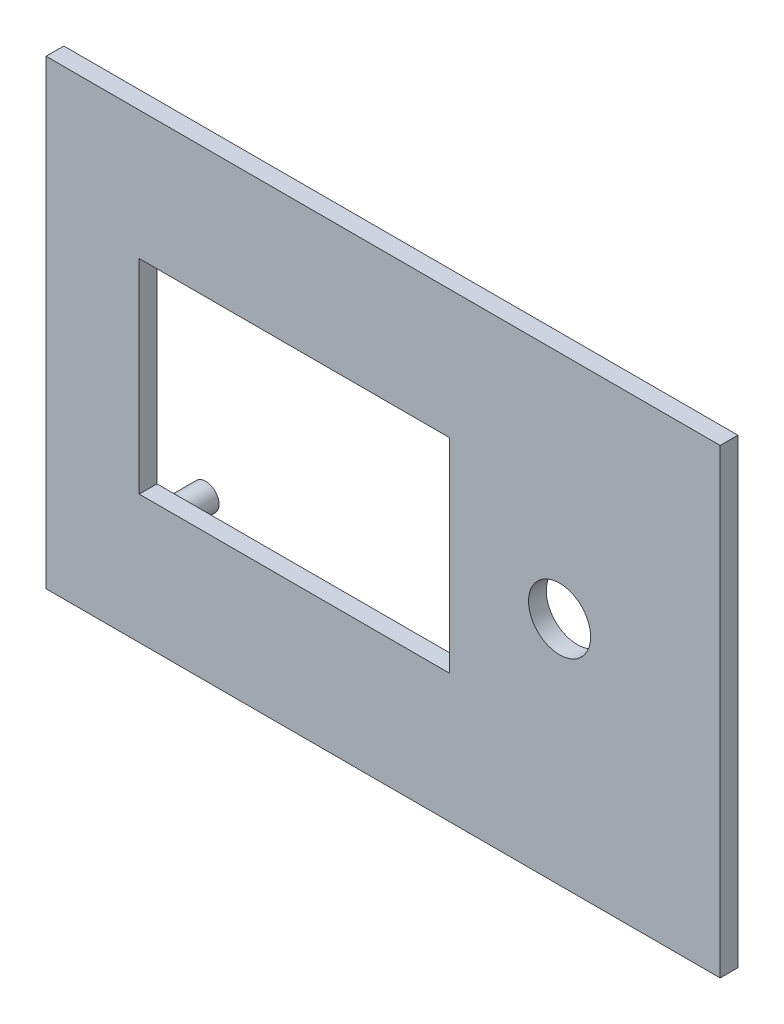
SolidWorks part; units mm, degrees
ref_plane "Ebene vorne" through (0, 0, 0) normal (0, 0, 1) x (1, 0, 0)
ref_plane "Ebene oben" through (0, 0, 0) normal (0, 1, 0) x (1, 0, 0)
ref_plane "Ebene rechts" through (0, 0, 0) normal (1, 0, 0) x (0, 0, -1)
sketch "Skizze10" plane through (0, 0, 0) normal (0, 0, 1) x (1, 0, 0)
  line L1 (-56.4904, -2.4023) -> (19.5096, -2.4023)
  line L2 (-56.4904, -2.4023) -> (-56.4904, -54.4023)
  line L3 (-56.4904, -54.4023) -> (19.5096, -54.4023)
  line L4 (19.5096, -2.4023) -> (19.5096, -54.4023)
  dimension "D1" = 76
  dimension "D2" = 52
extrude "Aufsatz-Linear austragen8" add sketch "Skizze10" along normal blind 2
sketch "Skizze11" plane through (0, 0, 2) normal (0, 0, 1) x (1, 0, 0)
  line L0 (-53.3332, -28.4023) -> (19.5096, -28.4023) construction
  line L1 (-45.987, -16.9023) -> (-10.987, -16.9023)
  line L2 (-45.987, -16.9023) -> (-45.987, -39.9023)
  line L3 (-45.987, -39.9023) -> (-10.987, -39.9023)
  line L4 (-10.987, -16.9023) -> (-10.987, -39.9023)
  line L5 (19.5096, -54.4023) -> (19.5096, -2.4023) construction
  point P6 (19.5096, -28.4023)
  dimension "D1" = 35
  dimension "D2" = 23
extrude "Schnitt-Linear austragen3" cut sketch "Skizze11" against normal blind 2
sketch "Skizze13" plane through (0, 0, 2) normal (0, 0, 1) x (1, 0, 0)
  line L1 (-53.9033, -28.4023) -> (16.6088, -28.4023) construction
  line L2 (-10.987, -16.9023) -> (-45.987, -16.9023) construction
  line L3 (-45.987, -39.9023) -> (-10.987, -39.9023) construction
  circle A0 centre (1.4022, -28.4023) radius 3.5
  point P2 (2.7784, -26.8523)
  point P3 (1.4022, -28.4023)
  point P5 (0, 0)
  point P8 (2.7784, 0.7098)
  point P9 (2.6375, 6.7112)
  point P10 (2.7784, -3.8165)
  point P15 (-53.9033, -28.4023)
  point P16 (16.6088, -28.4023)
  point P17 (1.9388, -28.4023)
  dimension "D1" = 7
extrude "Schnitt-Linear austragen4" cut sketch "Skizze13" against normal blind 2 contours A0
sketch "Skizze14" plane through (0, 0, 0) normal (0, 0, -1) x (-1, 0, 0)
  line L0 (10.987, -16.9023) -> (45.987, -16.9023) construction
  line L1 (45.987, -39.9023) -> (10.987, -39.9023) construction
  line L2 (45.987, -39.9023) -> (10.987, -39.9023) construction
  line L5 (45.987, -16.9023) -> (45.987, -39.9023) construction
  line L6 (10.987, -39.9023) -> (10.987, -16.9023) construction
  circle A0 centre (44.487, -14.4023) radius 1.5
  circle A1 centre (44.487, -42.4023) radius 1.5
  circle A2 centre (12.487, -14.4023) radius 1.5
  circle A3 centre (12.487, -42.4023) radius 1.5
  point P2 (0, 0)
  point P3 (12.6089, -14.8218)
  point P4 (-2.6031, -10.6074)
  point P5 (44.0666, -14.8218)
  point P6 (13.1764, -41.8896)
  point P7 (31.0085, -33.3569)
  point P8 (-2.6031, -10.6074)
  point P11 (31.0085, -65.0991)
  point P12 (31.0085, -64.5939)
  point P13 (44.0666, -41.8896)
  point P17 (3.7171, -32.868)
  point P18 (-2.6031, -10.6074)
  point P19 (1.0575, -33.4369)
  point P20 (-2.6031, -10.6074)
  point P21 (3.1031, -33.8342)
  point P22 (0.0732, -32.868)
  point P25 (0.0732, -64.868)
  point P26 (-2.6031, -10.6074)
  point P29 (3.0085, -64.868)
  point P30 (3.0085, -32.868)
  dimension "D1" = 3
  dimension "D6" = 3
  dimension "D7" = 3
  dimension "D8" = 3
  dimension "D2" = 2.5
  dimension "D3" = 2.5
  dimension "D4" = 2.5
  dimension "D5" = 2.5
extrude "Aufsatz-Linear austragen9" add sketch "Skizze14" along normal blind 4
